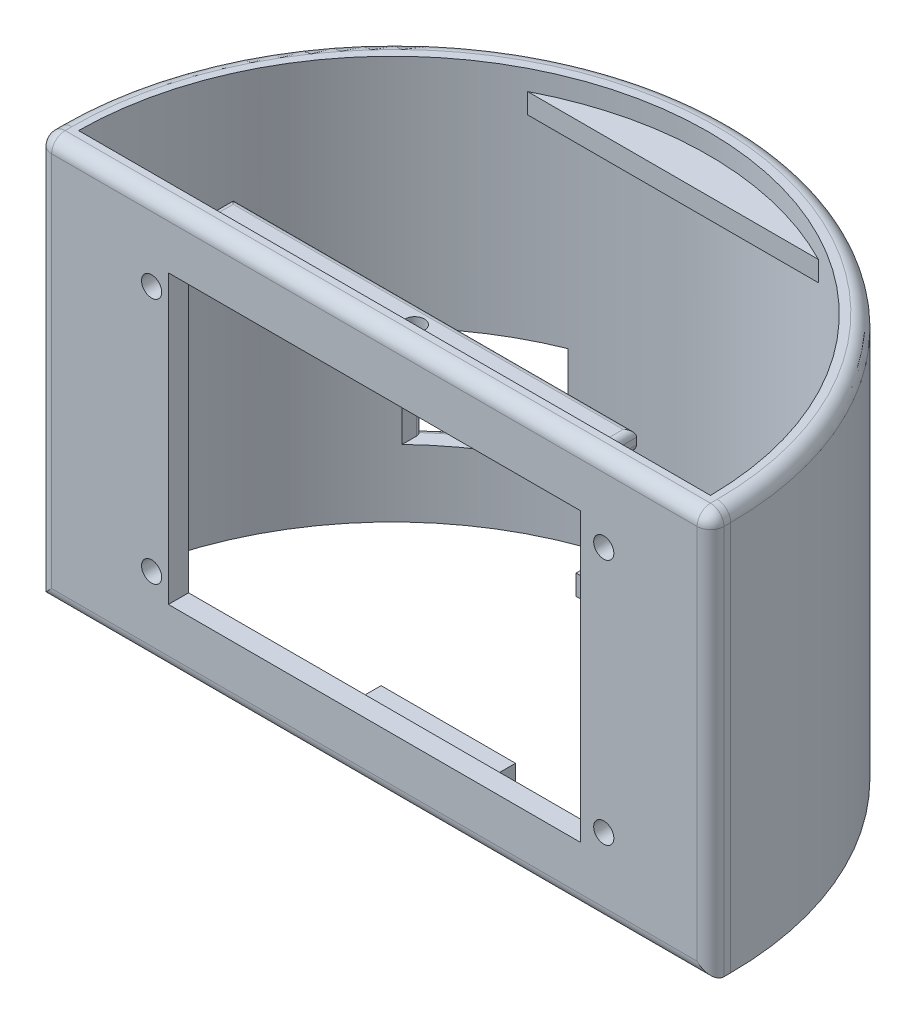
SolidWorks part; units mm, degrees
ref_plane "Front Plane" through (0, 0, 0) normal (0, 0, 1) x (1, 0, 0)
ref_plane "Top Plane" through (0, 0, 0) normal (0, 1, 0) x (1, 0, 0)
ref_plane "Right Plane" through (0, 0, 0) normal (1, 0, 0) x (0, 0, -1)
sketch "Sketch1" plane through (0, 0, 0) normal (0, 0, 1) x (1, 0, 0)
  line L1 (0, 0) -> (100, 0)
  line L2 (0, 0) -> (0, 60)
  line L3 (0, 60) -> (100, 60)
  line L4 (100, 0) -> (100, 60)
  line L5 (0, 0) -> (100, 60) construction
  line L6 (0, 60) -> (100, 0) construction
  line L7 (19.37, 8.64) -> (80.63, 8.64)
  line L8 (19.37, 8.64) -> (19.37, 51.36)
  line L9 (19.37, 51.36) -> (80.63, 51.36)
  line L10 (80.63, 8.64) -> (80.63, 51.36)
  line L11 (19.37, 8.64) -> (80.63, 51.36) construction
  line L12 (19.37, 51.36) -> (80.63, 8.64) construction
  circle A0 centre (84.12, 48.36) radius 1.5
  circle A1 centre (16.87, 48.36) radius 1.5
  circle A2 centre (16.87, 11.64) radius 1.5
  circle A3 centre (84.12, 11.64) radius 1.5
  point P4 (50, 30)
  point P10 (50, 30)
  dimension "D5" = 3
  dimension "D6" = 3
  dimension "D8" = 3
  dimension "D12" = 3
  dimension "D1" = 100
  dimension "D2" = 60
  dimension "D3" = 61.26
  dimension "D4" = 42.72
  dimension "D7" = 3
  dimension "D9" = 3
  dimension "D10" = 2.5
  dimension "D11" = 2.5
  dimension "D13" = 8.64
  dimension "D14" = 19.37
  dimension "D15" = 3.49
extrude "Front Face" add sketch "Sketch1" along normal blind 3
sketch "Sketch2" plane through (0, 0, 0) normal (0, 1, 0) x (1, 0, 0)
  line L0 (0, 0) -> (100, 0) construction
  line L1 (0, 0) -> (3, 0)
  line L2 (97, 0) -> (100, 0)
  arc A0 (0, 0) -> (100, 0) centre (50, 0) cw
  arc A1 (3, 0) -> (97, 0) centre (50, -0.3115) cw
  dimension "D1" = 50
  dimension "D2" = 3
  dimension "D3" = 3
extrude "Curved bck" add sketch "Sketch2" along normal up to surface (60 mm away) up to face at (50, 60, 1.5)
fillet "Fillet1" radius 2 4 edges at (0, 30, 3) (50, 0, 3) (100, 30, 3) (50, 60, 3) type face fillet first side face at (50, 30, 3) second side face at (50, 0, -11) second side face at (100, 30, 1.5) second side face at (50, 60, -23.3448) second side face at (0, 30, 1.5)
sketch "Sketch3" plane through (0, 0, 0) normal (0, 1, 0) x (1, 0, 0)
  line L0 (97, 0) -> (3, 0) construction
  line L1 (20, 0) -> (80, 0)
  line L2 (20, 0) -> (20, 6)
  line L3 (20, 6) -> (80, 6)
  line L4 (80, 0) -> (80, 6)
  line L5 (20, 0) -> (80, 6) construction
  line L6 (20, 6) -> (80, 0) construction
  circle A0 centre (50, 3) radius 1.45
  point P4 (50, 3)
  dimension "D4" = 2.9
  dimension "D1" = 6
  dimension "D2" = 60
  dimension "D3" = 17
extrude "Front retainer" add sketch "Sketch3" against normal blind 3 from offset 57 separate body
fillet "Fillet2" radius 1 3 edges at (20, 54, -3) (50, 54, -6) (80, 54, -3) type face fillet first side face at (50, 54, -1.55) second side face at (80, 55.5, -3) second side face at (50, 55.5, -6) second side face at (20, 55.5, -3)
fillet "Fillet3" radius 1 3 edges at (20, 57, -3) (50, 57, -6) (80, 57, -3) type face fillet first side face at (50, 57, -1.55) second side face at (20, 56, -3) second side face at (80, 56, -3) second side face at (50, 56, -6)
sketch "Sketch4" plane through (0, 0, 0) normal (0, 1, 0) x (1, 0, 0)
  line L0 (71.6207, 41.4215) -> (28.3793, 41.4215)
  arc A0 (28.3793, 41.4215) -> (71.6207, 41.4215) centre (50, -0.3115) cw
  arc A1 (97, 0) -> (3, 0) centre (50, -0.3115) ccw construction
  point P3 (50, 46.6896)
  point P7 (50, 46.6896)
extrude "Boss-Extrude4" add sketch "Sketch4" along normal blind 3 from offset 54
sketch "Sketch5" plane through (0, 0, 0) normal (0, 0, 1) x (1, 0, 0)
  line L0 (0, 0) -> (100, 0) construction
  line L1 (32.5, 25) -> (17.5, 25)
  line L2 (32.5, 25) -> (32.5, 10)
  line L3 (32.5, 10) -> (17.5, 10)
  line L4 (17.5, 25) -> (17.5, 10)
  line L5 (32.5, 25) -> (17.5, 10) construction
  line L6 (32.5, 10) -> (17.5, 25) construction
  point P4 (25, 17.5)
  dimension "D1" = 15
  dimension "D2" = 15
  dimension "D3" = 10
  dimension "D4" = 25
extrude "Cut-Extrude1" cut sketch "Sketch5" against normal blind 53 from offset 10 offset against normal yes
sketch "Sketch6" plane through (0, 0, 0) normal (0, 0, -1) x (-1, 0, 0)
  line L0 (-3, 0) -> (-97, 0) construction
  line L1 (-40, 0) -> (-60, 0)
  line L2 (-40, 0) -> (-40, 3)
  line L3 (-40, 3) -> (-60, 3)
  line L4 (-60, 0) -> (-60, 3)
  line L5 (-40, 0) -> (-60, 3) construction
  line L6 (-40, 3) -> (-60, 0) construction
  line L7 (-3, 60) -> (-3, 0) construction
  point P4 (-50, 1.5)
  dimension "D1" = 20
  dimension "D2" = 3
  dimension "D3" = 37
extrude "Boss-Extrude5" add sketch "Sketch6" along normal blind 8
sketch "Sketch7" plane through (0, 0, 0) normal (0, -1, 0) x (1, 0, 0)
  line L0 (40, -8) -> (40, 0) construction
  line L1 (60, -8) -> (40, -8) construction
  circle A0 centre (50, -4) radius 1.45
  dimension "D1" = 2.9
  dimension "D2" = 10
  dimension "D3" = 4
extrude "Cut-Extrude2" cut sketch "Sketch7" against normal blind 3
fillet "Fillet4" radius 2 1 edges at (50, 60, -50) type face fillet first side face at (50, 60, -23.3448) second side face at (24.8061, 17.5, -42.7461)
fillet "Fillet5" radius 1 4 edges at (24.6122, 10, -43.0751) (32.5, 17.5, -46.8375) (24.6122, 25, -43.0751) (17.5, 17.5, -37.9967) type face fillet first side face at (24.8061, 17.5, -42.7461) second side face at (24.7873, 25, -40.7907) second side face at (17.5, 17.5, -35.8194) second side face at (24.7873, 10, -40.7907) second side face at (32.5, 17.5, -45.0738)
sketch "Sketch9" plane through (0, 0, -8) normal (0, 0, -1) x (-1, 0, 0)
  line L1 (-60, 0) -> (-40, 0)
  line L2 (-60, 0) -> (-60, 3)
  line L3 (-60, 3) -> (-40, 3)
  line L4 (-40, 0) -> (-40, 3)
  line L5 (-60, 0) -> (-40, 3) construction
  line L6 (-60, 3) -> (-40, 0) construction
  point P4 (-50, 1.5)
extrude "Boss-Extrude6" add sketch "Sketch9" along normal blind 10 and the other way blind 1 from offset 30
sketch "Sketch10" plane through (0, 3, 0) normal (0, 1, 0) x (1, 0, 0)
  line L0 (40, 37) -> (60, 37) construction
  line L1 (40, 37) -> (40, 45.6134) construction
  circle A0 centre (50, 42) radius 1.45
  dimension "D1" = 2.9
  dimension "D2" = 5
  dimension "D3" = 10
extrude "Cut-Extrude3" cut sketch "Sketch10" against normal blind 10
equation "\"x\"=18.3922"
